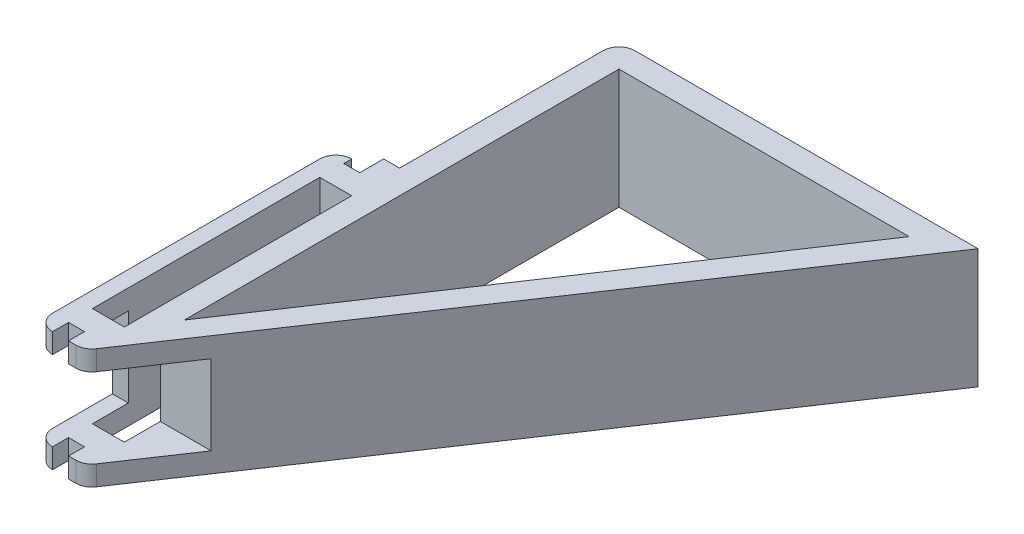
SolidWorks part; units mm, degrees
ref_plane "Front Plane" through (0, 0, 0) normal (0, 0, 1) x (1, 0, 0)
ref_plane "Top Plane" through (0, 0, 0) normal (0, 1, 0) x (1, 0, 0)
ref_plane "Right Plane" through (0, 0, 0) normal (1, 0, 0) x (0, 0, -1)
sketch "Sketch2" plane through (0, 0, 0) normal (0, 1, 0) x (1, 0, 0)
  line L0 (0, 0) -> (0, 2)
  line L1 (0, 2) -> (2, 2)
  line L2 (2, 2) -> (2, 0)
  line L3 (2, 0) -> (4, 0)
  line L4 (4, 0) -> (4, 39.5)
  line L5 (4, 39.5) -> (2, 39.5)
  line L6 (2, 39.5) -> (2, 36.5)
  line L7 (2, 36.5) -> (0, 36.5)
  line L8 (0, 36.5) -> (0, 37.5)
  line L9 (0, 37.5) -> (-2, 37.5)
  line L10 (-2, 37.5) -> (-2, 0)
  line L11 (-2, 0) -> (0, 0)
  line L12 (4, 0) -> (49, 67)
  line L13 (49, 67) -> (4, 67)
  line L14 (4, 67) -> (4, 39.5)
  line L15 (43.3712, 64) -> (45.8616, 62.3273)
  line L17 (0, 33.5) -> (4, 33.5)
  line L18 (7, 64) -> (43.3712, 64)
  line L19 (7, 9.5162) -> (43.3712, 64)
  line L20 (7, 64) -> (7, 9.5162)
  line L21 (0, 33.5) -> (0, 5)
  line L22 (0, 5) -> (4, 5)
  line L23 (4, 33.5) -> (4, 5)
  dimension "D1" = 34.5
  dimension "D2" = 2
  dimension "D3" = 2
  dimension "D4" = 6
  dimension "D5" = 2
  dimension "D6" = 1
  dimension "D7" = 2
  dimension "D8" = 3
  dimension "D9" = 27.5
  dimension "D10" = 45
  dimension "D11" = 3
  dimension "D12" = 3
  dimension "D13" = 3
  dimension "D14" = 3
  dimension "D15" = 3
extrude "Boss-Extrude1" add sketch "Sketch2" along normal blind 15 contours L10 L11 L0 L1 L2 L3 L4 L5 L6 L7 L8 L9 | L13 L14 L4 L12 region at (-1, 0, -0.3995) region at (4.8071, 0, -2.5)
sketch "Sketch3" plane through (-2, 0, 0) normal (-1, 0, 0) x (0, 0, 1)
  line L0 (0, 0) -> (0, 2.5)
  line L1 (0, 15) -> (0, 0) construction
  line L2 (0, 15) -> (0, 12.5)
  line L3 (0, 2.5) -> (-9.5, 2.5)
  line L4 (-9.5, 2.5) -> (-9.5, 12.5)
  line L5 (-9.5, 12.5) -> (0, 12.5)
  dimension "D1" = 2.5
  dimension "D2" = 2.5
  dimension "D3" = 9.5
extrude "Cut-Extrude1" cut sketch "Sketch3" against normal blind 15 and the other way through all
fillet "Fillet1" radius 2 1 edges at (-2, 7.5, -37.5) type face fillet first side face at (-2, 7.5, -11.75) second side face at (-1, 7.5, -37.5)
fillet "Fillet2" radius 2 1 edges at (4, 7.5, -67) type face fillet first side face at (4, 7.5, -53.25) second side face at (26.5, 7.5, -67)
fillet "Fillet3" radius 2 1 edges at (4, 1.25, 0) type face fillet first side face at (16.8451, 7.5, -19.125) first side face at (3, 13.75, 0) second side face at (3, 1.25, 0)
fillet "Fillet4" radius 2 1 edges at (4, 13.75, 0) type face fillet first side face at (16.9937, 7.5, -19.3462) second side face at (3, 13.75, 0)
fillet "Fillet5" radius 2 1 edges at (-2, 13.75, 0) type face fillet first side face at (-1, 13.75, 0) second side face at (-2, 7.5, -11.25)
fillet "Fillet6" radius 2 1 edges at (-2, 1.25, 0) type face fillet first side face at (-1, 1.25, 0) second side face at (-2, 7.5, -11.75)
